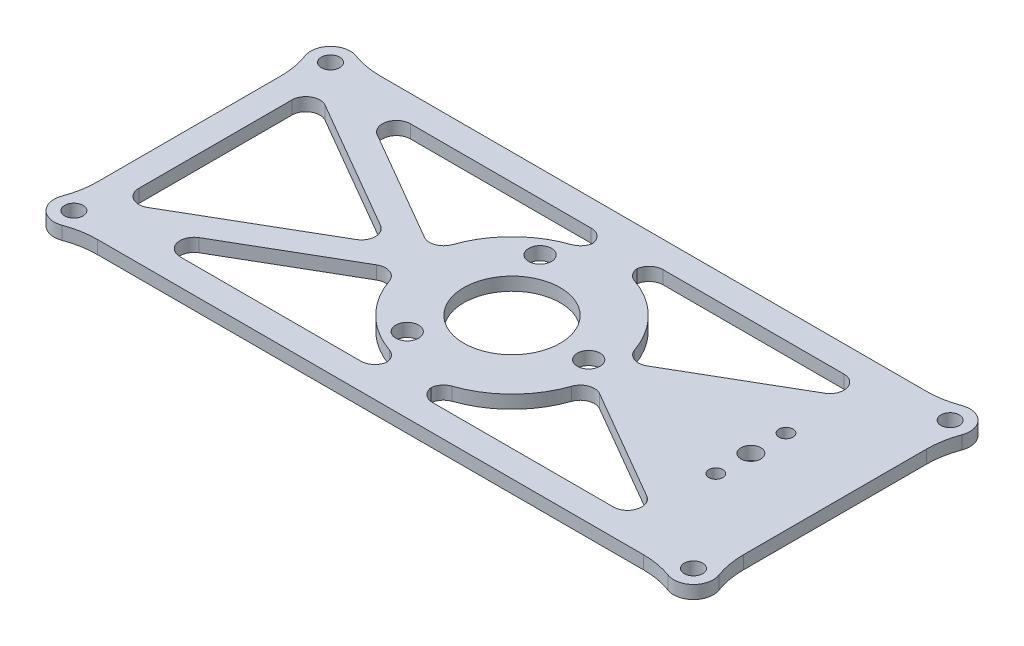
SolidWorks part; units mm, degrees
material "A-玻璃纤维"
ref_plane "前视基准面" through (0, 0, 0) normal (0, 0, 1) x (1, 0, 0)
ref_plane "上视基准面" through (0, 0, 0) normal (0, 1, 0) x (1, 0, 0)
ref_plane "右视基准面" through (0, 0, 0) normal (1, 0, 0) x (0, 0, -1)
other "Configuration Table"
sketch "草图1" plane through (0, 0, 0) normal (0, 1, 0) x (1, 0, 0)
  line L0 (0, 110.1479) -> (0, -92.6088) construction
  line L1 (0, 0) -> (70.6768, 29.2753) construction
  line L2 (-91.1768, 0) -> (88.5231, 0) construction
  line L3 (-70.6768, 29.2753) -> (70.6768, 29.2753) construction
  line L4 (-70.6768, 29.2753) -> (-70.6768, -29.2753) construction
  line L5 (-70.6768, -29.2753) -> (70.6768, -29.2753) construction
  line L6 (70.6768, -29.2753) -> (70.6768, 29.2753) construction
  line L7 (73.6768, -25.9212) -> (73.6768, 25.9212)
  line L8 (-67.3227, 32.2753) -> (67.3227, 32.2753)
  line L9 (-73.6768, 25.9212) -> (-73.6768, -25.9212)
  line L10 (-67.3227, -32.2753) -> (67.3227, -32.2753)
  line L11 (67.6768, -25.9212) -> (67.6768, 25.9212)
  line L12 (-67.3227, 26.2753) -> (67.3227, 26.2753)
  line L13 (-67.6768, 25.9212) -> (-67.6768, -25.9212)
  line L14 (-67.3227, -26.2753) -> (67.3227, -26.2753)
  line L15 (-73.6768, 32.2753) -> (73.6768, 32.2753) construction
  line L16 (-73.6768, 32.2753) -> (-73.6768, -32.2753) construction
  line L17 (-67.6768, 26.2753) -> (67.6768, 26.2753) construction
  line L18 (-67.6768, 26.2753) -> (-67.6768, -26.2753) construction
  line L19 (-73.6768, -32.2753) -> (73.6768, -32.2753) construction
  line L20 (-67.6768, -26.2753) -> (67.6768, -26.2753) construction
  line L21 (73.6768, -32.2753) -> (73.6768, 32.2753) construction
  line L22 (67.6768, -26.2753) -> (67.6768, 26.2753) construction
  circle A0 centre (0, 0) radius 76.5 construction
  circle A1 centre (70.6768, 29.2753) radius 2.1
  circle A2 centre (-70.6768, 29.2753) radius 2.1
  circle A3 centre (-70.6768, -29.2753) radius 2.1
  circle A4 centre (70.6768, -29.2753) radius 2.1
  arc A5 (73.6768, 25.9212) -> (67.3227, 32.2753) centre (70.6768, 29.2753) ccw
  arc A6 (-67.3227, 32.2753) -> (-73.6768, 25.9212) centre (-70.6768, 29.2753) ccw
  arc A7 (-73.6768, -25.9212) -> (-67.3227, -32.2753) centre (-70.6768, -29.2753) ccw
  arc A8 (67.6768, -25.9212) -> (67.3227, -26.2753) centre (70.6768, -29.2753) ccw
  arc A9 (-67.6768, 25.9212) -> (-67.3227, 26.2753) centre (-70.6768, 29.2753) ccw
  arc A10 (-67.3227, -26.2753) -> (-67.6768, -25.9212) centre (-70.6768, -29.2753) ccw
  arc A11 (67.3227, -32.2753) -> (73.6768, -25.9212) centre (70.6768, -29.2753) ccw
  arc A12 (67.3227, 26.2753) -> (67.6768, 25.9212) centre (70.6768, 29.2753) ccw
  circle B0 centre (-8.75, 15.1554) radius 2.6
  circle B1 centre (0, 0) radius 11
  circle B2 centre (-8.75, -15.1554) radius 2.6
  circle B3 centre (17.5, 0) radius 2.6
  circle B4 centre (0, 0) radius 22
  dimension "D1" = 153
  dimension "D3" = 4.2
  dimension "D4" = 9
  dimension "D5" = 3
  dimension "D2" = 67.5
  dimension "D6" = 3
sketch_block_instance "块-R1-滑环-2022-1"
sketch_block "块-R1-滑环-2022"
extrude "凸台-拉伸1" add sketch "草图1" along normal blind 3 contours L10 A11 L7 A5 L8 A6 L9 A7 A4 A3 A1 A2 L12 A12 L11 A8 L14 A10 L13 A9 | B4 B0 B1 B2 B3 region at (72.6932, 0, 31.2917) region at (-21.3777, 0, 0)
sketch "草图2" plane through (0, 3, 0) normal (0, 1, 0) x (1, 0, 0)
  line L0 (-67.3227, 26.2753) -> (-22, 0) construction
  line L1 (-22, 0) -> (-67.3227, -26.2753) construction
  line L2 (0, 22) -> (0, 26.2753) construction
  line L3 (-67.3227, 26.2753) -> (67.3227, 26.2753) construction
  line L4 (-5, 26.2753) -> (-5, 21.4243)
  line L5 (5, 26.2753) -> (5, 21.4243)
  line L6 (-1.65, 0) -> (1.65, 0) construction
  line L7 (0, -22) -> (0, -26.2753) construction
  line L8 (5, -26.2753) -> (5, -21.4243)
  line L9 (-5, -26.2753) -> (-5, -21.4243)
  line L10 (0, -1.65) -> (0, 1.65) construction
  line L11 (22, 0) -> (67.3227, -26.2753) construction
  line L12 (67.3227, 26.2753) -> (22, 0) construction
  line L13 (-67.6768, 23.0129) -> (-27.9815, 0)
  line L14 (-27.9815, 0) -> (-67.6768, -23.0129)
  line L15 (61.3412, 26.2753) -> (21.7478, 3.3215)
  line L16 (21.7478, -3.3215) -> (61.3412, -26.2753)
  line L17 (-61.3412, 26.2753) -> (-21.7478, 3.3215)
  line L18 (-21.7478, -3.3215) -> (-61.3412, -26.2753)
  line L19 (67.6768, 23.0129) -> (27.9815, 0)
  line L20 (27.9815, 0) -> (67.6768, -23.0129)
  line L21 (67.6768, -25.9212) -> (67.6768, 25.9212) construction
  line L22 (-67.3227, -26.2753) -> (67.3227, -26.2753) construction
  line L23 (-67.6768, 25.9212) -> (-67.6768, -25.9212) construction
  line L24 (67.6768, -25.9212) -> (67.6768, -23.0129)
  line L25 (-67.3227, -26.2753) -> (-61.3412, -26.2753)
  line L26 (-67.6768, 25.9212) -> (-67.6768, 23.0129)
  line L27 (-67.3227, 26.2753) -> (-61.3412, 26.2753)
  line L28 (-5, 26.2753) -> (5, 26.2753)
  line L29 (61.3412, 26.2753) -> (67.3227, 26.2753)
  line L30 (61.3412, -26.2753) -> (67.3227, -26.2753)
  line L31 (-5, -26.2753) -> (5, -26.2753)
  line L32 (-16.0185, 0) -> (-65.818, -28.8707) construction
  line L33 (-27.9815, 0) -> (-68.8273, -23.6799) construction
  line L34 (-67.6768, -23.0129) -> (-67.6768, -25.9212)
  line L35 (-65.818, 28.8707) -> (-16.0185, 0) construction
  line L36 (-68.8273, 23.6799) -> (-27.9815, 0) construction
  line L37 (65.818, 28.8707) -> (16.0185, 0) construction
  line L38 (68.8273, 23.6799) -> (27.9815, 0) construction
  line L39 (27.9815, 0) -> (68.8273, -23.6799) construction
  line L40 (16.0185, 0) -> (65.818, -28.8707) construction
  line L41 (67.6768, 23.0129) -> (67.6768, 25.9212)
  circle A0 centre (0, 0) radius 22 construction
  arc A1 (67.3227, 26.2753) -> (67.6768, 25.9212) centre (70.6768, 29.2753) ccw construction
  arc A2 (67.6768, -25.9212) -> (67.3227, -26.2753) centre (70.6768, -29.2753) ccw construction
  arc A3 (67.3227, 26.2753) -> (67.6768, 25.9212) centre (70.6768, 29.2753) ccw
  arc A4 (67.6768, -25.9212) -> (67.3227, -26.2753) centre (70.6768, -29.2753) ccw
  arc A5 (-67.3227, -26.2753) -> (-67.6768, -25.9212) centre (-70.6768, -29.2753) ccw construction
  arc A6 (-67.6768, 25.9212) -> (-67.3227, 26.2753) centre (-70.6768, 29.2753) ccw construction
  arc A7 (-67.3227, -26.2753) -> (-67.6768, -25.9212) centre (-70.6768, -29.2753) ccw
  arc A8 (-67.6768, 25.9212) -> (-67.3227, 26.2753) centre (-70.6768, 29.2753) ccw
  arc A9 (21.7478, -3.3215) -> (21.7478, 3.3215) centre (0, 0) ccw
  circle A10 centre (0, 0) radius 22
  arc A11 (5, 21.4243) -> (-5, 21.4243) centre (0, 0) ccw
  arc A12 (-5, -21.4243) -> (5, -21.4243) centre (0, 0) ccw
  arc A13 (-21.7478, 3.3215) -> (-21.7478, -3.3215) centre (0, 0) ccw
  dimension "D1" = 10
  dimension "D2" = 3
  dimension "D3" = 3
  dimension "D4" = 0
extrude "凸台-拉伸2" add sketch "草图2" against normal up to surface (3 mm away) up to face at (70.6768, 0, 31.3753)
fillet "圆角1" radius 3.2 19 edges at (-27.9815, 1.5, 0) (-67.6768, 1.5, 23.0129) (5, 1.5, 21.4243) (21.7478, 1.5, 3.3215) (61.3412, 1.5, 26.2753) (5, 1.5, 26.2753) (-5, 1.5, -21.4243) (-21.7478, 1.5, -3.3215) (-61.3412, 1.5, -26.2753) (-5, 1.5, -26.2753) (61.3412, 1.5, -26.2753) (21.7478, 1.5, -3.3215) (5, 1.5, -21.4243) (5, 1.5, -26.2753) (-61.3412, 1.5, 26.2753) (-21.7478, 1.5, 3.3215) (-5, 1.5, 21.4243) (-5, 1.5, 26.2753) (-67.6768, 1.5, -23.0129)
fillet "圆角2" radius 20 8 edges at (-67.3227, 1.5, 32.2753) (-73.6768, 1.5, 25.9212) (-73.6768, 1.5, -25.9212) (-67.3227, 1.5, -32.2753) (67.3227, 1.5, -32.2753) (73.6768, 1.5, 25.9212) (67.3227, 1.5, 32.2753) (73.6768, 1.5, -25.9212)
sketch "草图3" plane through (0, 3, 0) normal (0, 1, 0) x (1, 0, 0)
  line L0 (67.6768, 23.0129) -> (27.9815, 0)
  line L1 (27.9815, 0) -> (67.6768, -23.0129)
  line L2 (67.6768, -23.0129) -> (67.6768, 23.0129)
extrude "凸台-拉伸4" add sketch "草图3" against normal up to surface (3 mm away) up to face at (-24.2321, 0, 18.7337)
sketch "草图4" plane through (0, 3, 0) normal (0, 1, 0) x (1, 0, 0)
  line L0 (0, 0) -> (61.6673, 0) construction
  line L1 (54.5, 0) -> (54.5, 12.8668) construction
  line L2 (50.8645, 8) -> (53.7003, 8) construction
  line L3 (54.5, 0) -> (54.5, -10.9942) construction
  circle A0 centre (54.5, 0) radius 2.25
  circle A1 centre (54.5, 8) radius 1.6
  circle A2 centre (54.5, -8) radius 1.6
  dimension "D1" = 4.5
  dimension "D4" = 3.2
  dimension "D5" = 3.2
  dimension "D2" = 54.5
  dimension "D3" = 8
  dimension "D6" = 8
extrude "切除-拉伸1" cut sketch "草图4" against normal through all
